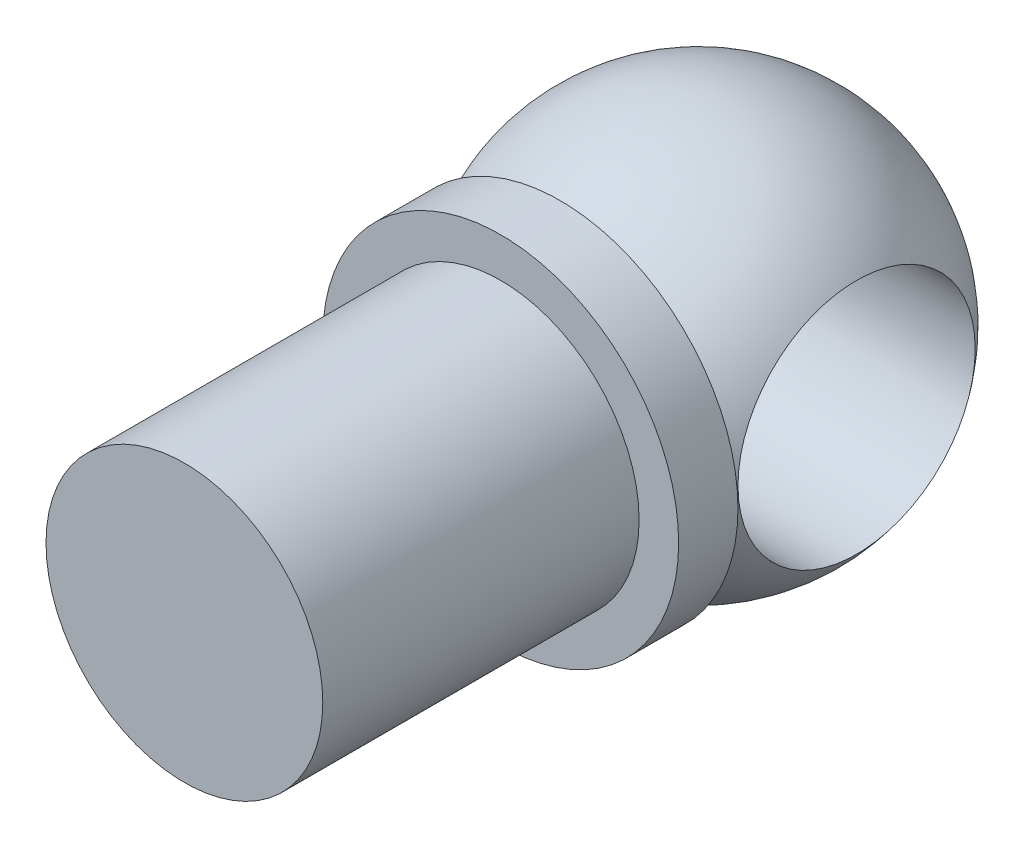
SolidWorks part; units mm, degrees
ref_plane "前视基准面" through (0, 0, 0) normal (0, 0, 1) x (1, 0, 0)
ref_plane "上视基准面" through (0, 0, 0) normal (0, 1, 0) x (1, 0, 0)
ref_plane "右视基准面" through (0, 0, 0) normal (1, 0, 0) x (0, 0, -1)
sketch "草图1" plane through (0, 0, 0) normal (0, 1, 0) x (1, 0, 0)
  line L1 (0, 0) -> (0, 5)
  line L2 (0, 5) -> (0, -5)
  arc A1 (0, 5) -> (0, -5) centre (0, 0) ccw
revolve "旋转5" add sketch "草图1" angle 360 about L2
sketch "草图5" plane through (0, 0, 0) normal (0, 0, 1) x (1, 0, 0)
  circle A0 centre (0, 0) radius 3.5
extrude "凸台-拉伸2" add sketch "草图5" along normal blind 13
sketch "草图6" plane through (0, 0, 0) normal (1, 0, 0) x (0, 0, -1)
  circle A0 centre (0, 0) radius 3
extrude "切除-拉伸2" cut sketch "草图6" against normal blind 13 and the other way blind 13
ref_plane "基准面1" through (0, 0, 5) normal (0, 0, 1) x (1, 0, 0)
sketch "草图7" plane through (0, 0, 5) normal (0, 0, 1) x (1, 0, 0)
  circle A0 centre (0, 0) radius 4.5
extrude "凸台-拉伸3" add sketch "草图7" against normal blind 1.5
sketch "草图8" plane through (0, 0, 0) normal (1, 0, 0) x (0, 0, -1)
  line L2 (-0.5, -0.5) -> (0.5, -0.5)
  line L3 (-0.5, -0.5) -> (-0.5, 0.5)
  line L4 (-0.5, 0.5) -> (0.5, 0.5)
  line L5 (0.5, -0.5) -> (0.5, 0.5)
  point P0 (0, 0)
